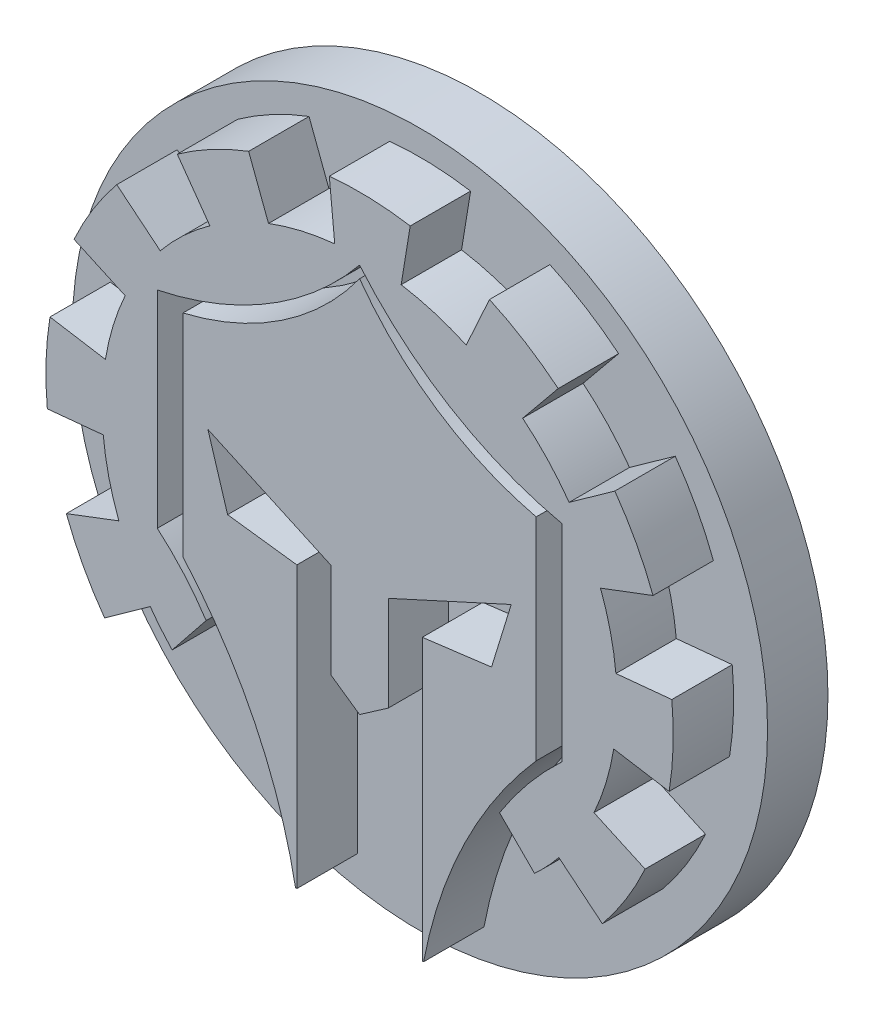
SolidWorks part; units mm, degrees
ref_plane "Front Plane" through (0, 0, 0) normal (0, 0, 1) x (1, 0, 0)
ref_plane "Top Plane" through (0, 0, 0) normal (0, 1, 0) x (1, 0, 0)
ref_plane "Right Plane" through (0, 0, 0) normal (1, 0, 0) x (0, 0, -1)
sketch "Sketch1" plane through (0, 0, 0) normal (0, 1, 0) x (1, 0, 0)
  line L0 (100.8063, 0) -> (100.8063, -127) construction
  line L1 (0, 0) -> (201.6125, 0)
  line L2 (0, 0) -> (0, -45.847)
  line L3 (0, -45.847) -> (34.944, -45.847)
  line L9 (19.05, -7.62) -> (182.5625, -7.62)
  line L10 (19.05, -7.62) -> (19.05, -38.2238)
  line L11 (19.05, -38.2238) -> (182.5625, -38.2238)
  line L12 (182.5625, -7.62) -> (182.5625, -38.2238)
  line L13 (60.344, -58.547) -> (73.2151, -58.547) construction
  line L14 (141.2685, -58.547) -> (171.549, -58.547) construction
  line L15 (74.2236, -72.4265) -> (74.2236, -91.8023) construction
  line L16 (127.3874, -72.4281) -> (127.3874, -64.5576) construction
  line L17 (166.6685, -45.847) -> (201.6125, -45.847)
  line L18 (182.5625, -22.9219) -> (-7.7585, -22.9219) construction
  line L22 (201.6125, 0) -> (201.6125, -45.847)
  line L29 (34.944, -45.847) -> (34.9441, -83.7692)
  line L30 (100.8063, -127) -> (100.8063, -142.2501) construction
  line L32 (166.6685, -45.847) -> (166.6685, -83.7692)
  line L34 (114.6874, -72.4281) -> (114.6874, -88.9176) construction
  line L35 (100.8063, -58.547) -> (112.2464, -58.547) construction
  line L36 (50.1841, -99.0092) -> (151.4284, -99.0092)
  line L37 (141.2685, -86.3092) -> (149.6169, -86.3092) construction
  circle A0 centre (60.344, -72.4265) radius 13.8795
  circle A1 centre (141.2685, -72.4281) radius 13.8811
  circle A2 centre (13.0969, -9.7139) radius 2.54
  circle A3 centre (188.5156, -9.7139) radius 2.54
  circle A4 centre (13.0969, -36.1299) radius 2.54
  circle A5 centre (188.5156, -36.1299) radius 2.54
  circle A10 centre (100.8063, -72.4281) radius 13.8811
  arc A23 (151.4284, -99.0092) -> (166.6685, -83.7692) centre (151.4285, -83.7692) ccw
  arc A24 (50.1841, -99.0092) -> (34.9441, -83.7692) centre (50.184, -83.7692) cw
  point P48 (166.6685, -99.0092)
  point P51 (34.9441, -99.0092)
  dimension "D7" = 27.759
  dimension "D16" = 5.08
  dimension "D33" = 27.7622
  dimension "D21" = 27.7622
  dimension "D22" = 15.24
  dimension "D1" = 201.6125
  dimension "D2" = 30.6038
  dimension "D3" = 163.5125
  dimension "D4" = 19.05
  dimension "D5" = 45.847
  dimension "D6" = 7.62
  dimension "D9" = 12.7
  dimension "D14" = 175.4187
  dimension "D15" = 87.7094
  dimension "D17" = 26.416
  dimension "D18" = 13.208
  dimension "D19" = 26.416
  dimension "D20" = 13.208
  dimension "D8" = 25.4
  dimension "D10" = 12.7
  dimension "D11" = 25.4
  dimension "D12" = 12.7
  dimension "D13" = 12.7
extrude "Boss-Extrude1" add sketch "Sketch1" along normal blind 5.08
sketch "Sketch3" plane through (0, 0, 198.0184) normal (0, 1, 0) x (-1, 0, 0)
  line L12 (-50.1841, -99.0092) -> (-151.4284, -99.0092) construction
  line L14 (-50.0063, -101.5492) -> (-151.6062, -101.5492)
  line L21 (-50.0063, -101.5492) -> (-50.0063, -99.0092)
  line L22 (-50.0063, -99.0092) -> (-151.6062, -99.0092)
  line L23 (-151.6062, -99.0092) -> (-151.6062, -101.5492)
  point P3 (-100.8063, -101.5492)
  point P7 (-100.8063, -99.0092)
  point P10 (-100.8063, -99.0092)
  dimension "D1" = 101.6
  dimension "D2" = 2.54
extrude "Boss-Extrude4" add sketch "Sketch3" against normal blind 38.1
sketch "Sketch7" plane through (0, 0, 99.0092) normal (0, 0, -1) x (1, 0, 0)
  line L1 (96.9962, 33.02) -> (104.6162, 33.02)
  line L2 (96.9962, 33.02) -> (96.9962, 38.1)
  line L3 (96.9962, 38.1) -> (104.6162, 38.1)
  line L4 (104.6162, 33.02) -> (104.6162, 38.1)
  line L7 (151.6062, 38.1) -> (151.6062, 0) construction
  line L9 (50.0063, 38.1) -> (151.6062, 38.1) construction
  dimension "D1" = 46.99
  dimension "D2" = 7.62
  dimension "D3" = 5.08
  dimension "D4" = 0
extrude "Boss-Extrude5" add sketch "Sketch7" along normal blind 11.43
fillet "Fillet5" 2 edges at (104.6162, -35.56, 87.5792) (96.9962, -35.56, 87.5792) type full round first side face at (104.6162, -35.56, 92.0242) second side face at (96.9962, -35.56, 92.0242) middle face at (100.8062, -35.56, 87.5792)
sketch "Sketch12" plane through (201.6125, 0, 0) normal (1, 0, 0) x (0, 0, -1)
  line L2 (0, 0) -> (-155.0308, 0)
  line L3 (0, 0) -> (0, 26.8372)
  line L4 (0, 26.8372) -> (-155.0308, 26.8372)
  line L5 (-155.0308, 0) -> (-155.0308, 26.8372)
sketch "Sketch14" plane through (0, 0, 99.0092) normal (0, 0, -1) x (-1, 0, 0)
  line L0 (199.3383, 310.1514) -> (657.3383, 310.1514) construction
  line L1 (-106.6923, -23.8525) -> (-108.1651, -25.3252)
  line L2 (-94.3545, -23.0235) -> (-92.9253, -24.8077)
  line L3 (-109.3118, -20.69) -> (-109.3118, -12.0094)
  line L4 (-92.301, -20.69) -> (-92.301, -12.0094)
  line L5 (-100.8062, -23.2208) -> (-99.5994, -22.3806)
  line L6 (-99.5994, -22.3806) -> (-99.5994, -18.3831)
  line L7 (-99.5994, -18.3831) -> (-94.428, -16.0226)
  line L8 (-94.428, -16.0226) -> (-95.2573, -18.7163)
  line L9 (-95.2573, -18.7163) -> (-98.169, -19.0875)
  line L10 (-98.169, -19.0875) -> (-98.169, -30.8772)
  line L11 (-98.169, -30.8772) -> (-98.1134, -30.8772)
  line L12 (-93.3803, -21.1933) -> (-93.3803, -12.3078)
  line L13 (-103.4991, -30.8772) -> (-103.4435, -30.8772)
  line L14 (-108.2322, -21.1933) -> (-108.2322, -12.3078)
  line L15 (-107.1845, -16.0226) -> (-106.3552, -18.7163)
  line L16 (-106.3552, -18.7163) -> (-103.4435, -19.0875)
  line L17 (-102.0131, -18.3831) -> (-107.1845, -16.0226)
  line L18 (-102.0131, -22.3806) -> (-102.0131, -18.3831)
  line L19 (-100.8062, -23.2208) -> (-102.0131, -22.3806)
  line L20 (-103.4435, -19.0875) -> (-103.4435, -30.8772)
  line L21 (-109.188, -24.2376) -> (-111.0162, -25.7334)
  line L22 (-110.6636, -21.8648) -> (-112.8137, -22.8431)
  line L23 (-90.6831, -21.2276) -> (-88.475, -22.0669)
  line L24 (-90.0847, -25.0658) -> (-92.0045, -23.6895)
  line L25 (-100.8062, -23.2208) -> (-100.8062, -7.3481) construction
  line L26 (-100.8062, -6.8497) -> (-100.8062, -4.1876) construction
  line L27 (-111.494, -19.1279) -> (-113.8252, -19.5092)
  line L28 (-111.5856, -16.3352) -> (-113.9368, -16.1074)
  line L29 (-110.9363, -13.5498) -> (-113.1458, -12.7144)
  line L30 (-109.6192, -11.0855) -> (-111.5415, -9.7126)
  line L31 (-107.6642, -8.9979) -> (-109.16, -7.1697)
  line L32 (-105.2914, -7.5223) -> (-106.2698, -5.3722)
  line L33 (-102.5545, -6.6919) -> (-102.9358, -4.3606)
  line L34 (-99.7619, -6.6003) -> (-99.5341, -4.2491)
  line L35 (-96.9764, -7.2496) -> (-96.141, -5.0401)
  line L36 (-94.5121, -8.5667) -> (-93.1392, -6.6444)
  line L37 (-92.4245, -10.5217) -> (-90.5963, -9.0259)
  line L38 (-90.9489, -12.8944) -> (-88.7988, -11.9161)
  line L39 (-90.1185, -15.6314) -> (-87.7873, -15.2501)
  line L40 (-90.0269, -18.424) -> (-87.6757, -18.6518)
  line L42 (-151.6062, -38.1) -> (-151.6062, 0) construction
  line L49 (-107.1004, -26.1926) -> (-108.4733, -28.1149) [skipped]
  line L50 (-104.6361, -27.5096) -> (-105.4715, -29.7192) [skipped]
  line L51 (-101.8506, -28.159) -> (-102.0784, -30.5102) [skipped]
  line L52 (-99.058, -28.0674) -> (-98.6767, -30.3986) [skipped]
  line L53 (-96.3211, -27.237) -> (-95.3427, -29.3871) [skipped]
  line L54 (-93.9483, -25.7614) -> (-92.4525, -27.5896) [skipped]
  line L55 (-90.6762, -21.2095) -> (-88.4667, -22.0449) [skipped]
  line L56 (-91.9933, -23.6738) -> (-90.071, -25.0466) [skipped]
  arc A0 (-108.1651, -25.3252) -> (-109.188, -24.2376) centre (-100.8062, -17.3796) cw
  arc A1 (-106.6923, -23.8525) -> (-109.3118, -20.69) centre (-120.3142, -32.4693) ccw
  arc A2 (-94.3545, -23.0235) -> (-92.301, -20.69) centre (-85.0837, -29.1115) cw
  arc A3 (-109.3118, -12.0094) -> (-100.8062, -6.8497) centre (-112.667, 3.112) ccw
  arc A4 (-92.301, -12.0094) -> (-100.8062, -6.8497) centre (-89.2554, 2.6009) cw
  arc A5 (-98.1134, -30.8772) -> (-93.3803, -21.1933) centre (-78.0697, -34.675) cw
  arc A6 (-93.3803, -12.3078) -> (-100.8062, -7.3481) centre (-90.4186, 0.1657) cw
  arc A7 (-108.2322, -12.3078) -> (-100.8062, -7.3481) centre (-111.1939, 0.1657) ccw
  arc A8 (-103.4991, -30.8772) -> (-108.2322, -21.1933) centre (-123.5428, -34.675) ccw
  arc A9 (-111.0162, -25.7334) -> (-112.8137, -22.8431) centre (-100.8062, -17.3796) cw
  arc A10 (-113.8252, -19.5092) -> (-113.9368, -16.1074) centre (-100.8062, -17.3796) cw
  arc A11 (-110.6636, -21.8648) -> (-111.494, -19.1279) centre (-100.8062, -17.3796) cw
  arc A12 (-111.5856, -16.3352) -> (-110.9363, -13.5498) centre (-100.8062, -17.3796) cw
  arc A13 (-113.1458, -12.7144) -> (-111.5415, -9.7126) centre (-100.8062, -17.3796) cw
  arc A14 (-109.16, -7.1697) -> (-106.2698, -5.3722) centre (-100.8062, -17.3796) cw
  arc A15 (-109.6192, -11.0855) -> (-107.6642, -8.9979) centre (-100.8062, -17.3796) cw
  arc A16 (-102.9358, -4.3606) -> (-99.5341, -4.2491) centre (-100.8062, -17.3796) cw
  arc A17 (-105.2914, -7.5223) -> (-102.5545, -6.6919) centre (-100.8062, -17.3796) cw
  arc A18 (-96.141, -5.0401) -> (-93.1392, -6.6444) centre (-100.8062, -17.3796) cw
  arc A19 (-99.7619, -6.6003) -> (-96.9764, -7.2496) centre (-100.8062, -17.3796) cw
  arc A20 (-94.5121, -8.5667) -> (-92.4245, -10.5217) centre (-100.8062, -17.3796) cw
  arc A21 (-90.5963, -9.0259) -> (-88.7988, -11.9161) centre (-100.8062, -17.3796) cw
  arc A22 (-90.9489, -12.8944) -> (-90.1185, -15.6314) centre (-100.8062, -17.3796) cw
  arc A23 (-87.7873, -15.2501) -> (-87.6757, -18.6518) centre (-100.8062, -17.3796) cw
  arc A24 (-90.0269, -18.424) -> (-90.6831, -21.2276) centre (-100.8062, -17.3796) cw
  arc A25 (-88.475, -22.0669) -> (-90.0847, -25.0658) centre (-100.8062, -17.3796) cw
  arc A26 (-92.0045, -23.6895) -> (-92.9253, -24.8077) centre (-100.8062, -17.3796) cw
  point P16 (-100.8062, -6.8497)
  point P101 (-100.8062, -17.3796)
  dimension "D3" = 50.8
  dimension "D1" = 2.0828
  dimension "D2" = 2.286
  dimension "D4" = 50.8
  dimension "D5" = 2.3622
  dimension "D6" = 2.3622
  dimension "D11" = 3.4036
  dimension "D12" = 3.4036
  dimension "D13" = 12
extrude "Boss-Extrude6" add sketch "Sketch14" against normal blind 2.54 contours L13 L20 L16 L15 L17 L18 L19 L5 L6 L7 L8 L9 L10 L11 A5 L12 A6 A7 L14 A8 | L40 A23 L39 A22 L38 A21 L37 A20 L36 A18 L35 A19 L34 A16 L33 A17 L32 A14 L31 A15 L30 A13 L29 A12 L28 A10 L27 A11 L22 A9 L21 A0 L1 A1 L3 A3 A4 L4 A2 L2 A26 L24 A25 L23 A24
sketch "Sketch15" plane through (0, 0, 0) normal (0, -1, 0) x (1, 0, 0)
  line L0 (121.0374, 88.8492) -> (121.0374, 58.7984) construction
  line L2 (100.8063, 72.4281) -> (100.8063, 116.3624) construction
  line L3 (114.6873, 88.8492) -> (114.6873, 96.4692)
  line L4 (151.6062, 96.4692) -> (50.0063, 96.4692) construction
  line L5 (127.3874, 88.8492) -> (127.3874, 96.4692)
  line L6 (127.3874, 96.4692) -> (114.6873, 96.4692)
  line L7 (74.2251, 96.4692) -> (86.9252, 96.4692)
  line L8 (74.2251, 88.8492) -> (74.2251, 96.4692)
  line L9 (86.9252, 88.8492) -> (86.9252, 96.4692)
  line L10 (100.8063, 72.4281) -> (121.0374, 88.8492) construction
  line L11 (100.8063, 72.4281) -> (80.5752, 88.8492) construction
  line L12 (100.8063, 72.4281) -> (135.1371, 72.4281) construction
  circle A2 centre (121.0374, 88.8492) radius 1.8415
  arc A3 (114.6873, 88.8492) -> (127.3874, 88.8492) centre (121.0374, 88.8492) ccw
  arc A4 (86.9252, 88.8492) -> (74.2251, 88.8492) centre (80.5752, 88.8492) cw
  circle A5 centre (80.5752, 88.8492) radius 1.8415
  dimension "D1" = 39.065
  dimension "D4" = 3.683
  dimension "D3" = 20.2311
extrude "Boss-Extrude7" add sketch "Sketch15" along normal blind 2.54
sketch "Sketch19" plane through (0, 0, 0) normal (0, -1, 0) x (1, 0, 0)
  circle A0 centre (80.5752, 88.8492) radius 1.8415
  circle A1 centre (121.0374, 88.8492) radius 1.8415
  dimension "D1" = 3.683
  dimension "D2" = 3.683
extrude "Cut-Extrude3" cut sketch "Sketch19" against normal blind 5.08
extrude "Cut-Extrude4" cut sketch "Sketch12" against normal through all
sketch "Sketch21" plane through (0, 0, 99.0092) normal (0, 0, 1) x (1, 0, 0)
  line L0 (55.0863, -33.02) -> (55.0863, -25.8358)
  line L1 (55.0863, -5.08) -> (55.8831, -5.08)
  line L2 (50.0063, -38.1) -> (50.0063, 0) construction
  line L3 (50.0063, 0) -> (151.6062, 0) construction
  line L4 (55.0863, -33.02) -> (62.2705, -33.02)
  line L5 (91.9162, -33.02) -> (91.9162, -30.7371)
  line L6 (146.5263, -5.08) -> (145.7294, -5.08)
  line L7 (96.9962, -38.1) -> (96.9962, -33.02) construction
  line L8 (109.6962, -33.02) -> (114.1973, -33.02)
  line L9 (146.5263, -33.02) -> (146.5263, -25.8358)
  line L10 (139.342, -33.02) -> (146.5263, -25.8358)
  line L11 (50.0063, -38.1) -> (151.6062, -38.1) construction
  line L12 (151.6062, -38.1) -> (151.6062, 0) construction
  line L13 (109.6962, -33.02) -> (109.6962, -30.7371)
  line L14 (104.6162, -33.02) -> (104.6162, -38.1) construction
  line L15 (135.7499, -33.02) -> (146.5263, -22.2437)
  line L16 (128.5657, -33.02) -> (146.5263, -15.0595)
  line L17 (124.1768, -5.08) -> (115.9162, -13.3406)
  line L18 (124.9736, -33.02) -> (146.5263, -11.4674)
  line L19 (117.7894, -33.02) -> (145.7294, -5.08)
  line L20 (114.1973, -33.02) -> (142.1373, -5.08)
  line L21 (120.5847, -5.08) -> (114.9079, -10.7568)
  line L22 (134.9531, -5.08) -> (114.4674, -25.5657)
  line L23 (131.361, -5.08) -> (116.3743, -20.0667)
  line L24 (113.4005, -5.08) -> (111.8988, -6.5817)
  line L25 (100.8063, -17.7484) -> (100.8063, 4.9484) construction
  line L26 (62.2705, -33.02) -> (55.0863, -25.8358)
  line L27 (65.8626, -33.02) -> (55.0863, -22.2437)
  line L28 (73.0468, -33.02) -> (55.0863, -15.0595)
  line L29 (76.6389, -33.02) -> (55.0863, -11.4674)
  line L30 (83.8231, -33.02) -> (55.8831, -5.08)
  line L31 (87.4152, -33.02) -> (59.4752, -5.08)
  line L32 (66.6594, -5.08) -> (87.1451, -25.5657)
  line L33 (70.2515, -5.08) -> (85.2382, -20.0667)
  line L34 (77.4357, -5.08) -> (85.6963, -13.3406)
  line L35 (81.0278, -5.08) -> (86.7046, -10.7568)
  line L36 (88.212, -5.08) -> (89.7137, -6.5817)
  line L37 (120.5847, -5.08) -> (113.4005, -5.08)
  line L38 (131.361, -5.08) -> (124.1768, -5.08)
  line L39 (117.7894, -33.02) -> (124.9736, -33.02)
  line L40 (142.1373, -5.08) -> (134.9531, -5.08)
  line L41 (128.5657, -33.02) -> (135.7499, -33.02)
  line L42 (146.5263, -11.4674) -> (146.5263, -5.08)
  line L43 (139.342, -33.02) -> (146.5263, -33.02)
  line L44 (146.5263, -22.2437) -> (146.5263, -15.0595)
  line L45 (81.0278, -5.08) -> (88.212, -5.08)
  line L46 (70.2515, -5.08) -> (77.4357, -5.08)
  line L47 (59.4752, -5.08) -> (66.6594, -5.08)
  line L48 (87.4152, -33.02) -> (91.9162, -33.02)
  line L49 (76.6389, -33.02) -> (83.8231, -33.02)
  line L50 (55.0863, -11.4674) -> (55.0863, -5.08)
  line L51 (55.0863, -22.2437) -> (55.0863, -15.0595)
  line L52 (65.8626, -33.02) -> (73.0468, -33.02)
  arc A0 (91.9162, -30.7371) -> (87.1451, -25.5657) centre (100.8063, -17.7484) cw
  arc A1 (111.8988, -6.5817) -> (114.9079, -10.7568) centre (100.8063, -17.7484) cw
  arc A2 (115.9162, -13.3406) -> (116.3743, -20.0667) centre (100.8063, -17.7484) cw
  arc A3 (114.4674, -25.5657) -> (109.6962, -30.7371) centre (100.8063, -17.7484) cw
  arc A4 (86.7046, -10.7568) -> (89.7137, -6.5817) centre (100.8063, -17.7484) cw
  arc A5 (85.2382, -20.0667) -> (85.6963, -13.3406) centre (100.8063, -17.7484) cw
  dimension "D4" = 5.08
  dimension "D1" = 5.08
  dimension "D2" = 5.08
  dimension "D3" = 5.08
  dimension "D5" = 5.08
  dimension "D6" = 5.08
  dimension "D7" = 5.08
  dimension "D8" = 2.54
  dimension "D9" = 5.08
  dimension "D10" = 2.54
  dimension "D11" = 45
  dimension "D12" = 5.08
  dimension "D13" = 2.54
  dimension "D14" = 5.08
  dimension "D15" = 2.54
  dimension "D16" = 5.08
  dimension "D17" = 2.54
  dimension "D18" = 5.08
extrude "Cut-Extrude5" cut sketch "Sketch21" against normal blind 2.54
fillet "Fillet6" radius 2.54 2 edges at (151.6062, -19.05, 99.0092) (50.0063, -19.05, 99.0092)
sketch "Sketch22" plane through (0, -33.02, 0) normal (0, 1, 0) x (1, 0, 0)
  line L0 (100.8063, -96.4692) -> (100.8063, -88.8492) construction
  line L1 (114.6873, -96.4692) -> (86.9252, -96.4692) construction
  line L2 (94.4563, -96.4692) -> (94.4563, -88.8492)
  line L3 (107.1563, -96.4692) -> (107.1563, -88.8492)
  line L4 (80.5752, -88.8492) -> (121.2071, -88.8492) construction
  line L5 (94.4563, -96.4692) -> (107.1563, -96.4692)
  arc A1 (107.1563, -88.8492) -> (94.4563, -88.8492) centre (100.8063, -88.8492) ccw
  point P4 (100.8063, -92.6592)
  dimension "D1" = 6.35
extrude "Boss-Extrude8" add sketch "Sketch22" against normal blind 5.08
sketch "Sketch23" plane through (0, -33.02, 0) normal (0, 1, 0) x (1, 0, 0)
  circle A0 centre (100.8063, -88.8492) radius 1.8415
  dimension "D1" = 3.683
extrude "Cut-Extrude6" cut sketch "Sketch23" against normal through all both and the other way through all
sketch "Sketch25" plane through (0, 0, 99.0092) normal (0, 0, 1) x (1, 0, 0)
  line L1 (27.5347, 16.0367) -> (157.9674, 16.0367)
  line L2 (27.5347, 16.0367) -> (27.5347, -40.6081)
  line L3 (27.5347, -40.6081) -> (157.9674, -40.6081)
  line L4 (157.9674, 16.0367) -> (157.9674, -40.6081)
  circle A1 centre (100.8063, -17.7484) radius 14.6177
extrude "Cut-Extrude8" cut sketch "Sketch25" against normal through all
equation "\"D15@Sketch1\"=\"D14@Sketch1\"/2"
equation "\"D18@Sketch1\"=\"D17@Sketch1\"/2"
equation "\"D19@Sketch1\"=\"D17@Sketch1\""
equation "\"D20@Sketch1\"=\"D18@Sketch1\""
